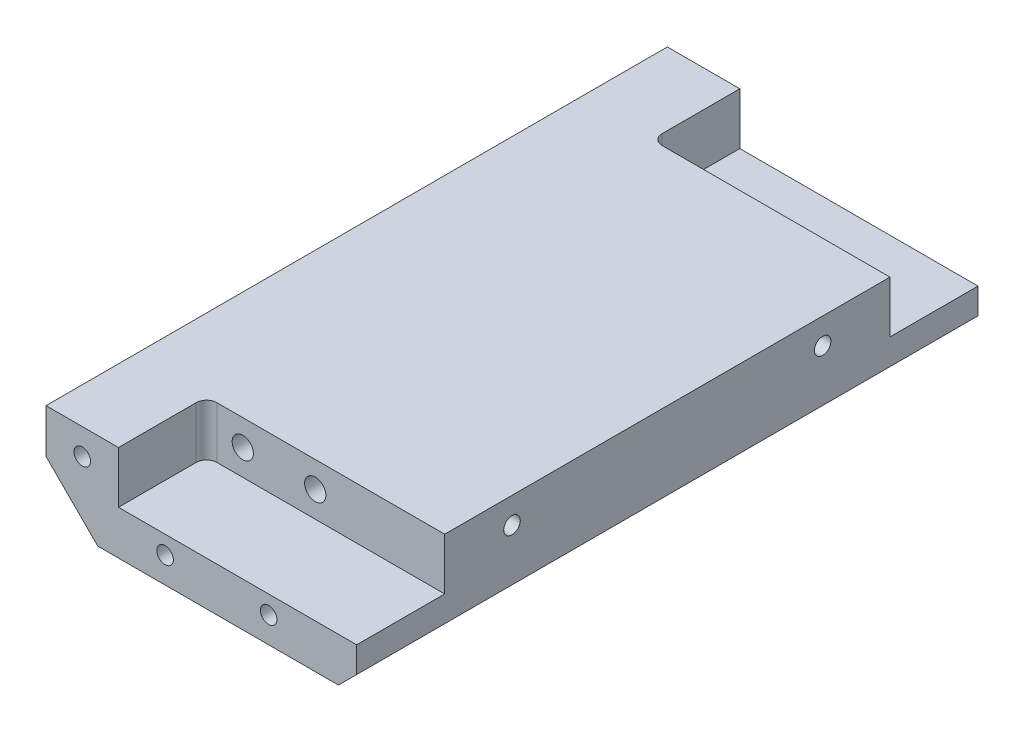
SolidWorks part; units mm, degrees
other "标注1"
sketch "草图22"
ref_plane "前视基准面" through (0, 0, 0) normal (0, 0, 1) x (1, 0, 0)
ref_plane "上视基准面" through (0, 0, 0) normal (0, 1, 0) x (1, 0, 0)
ref_plane "右视基准面" through (0, 0, 0) normal (1, 0, 0) x (0, 0, -1)
other "Configuration Table"
ref_plane "基准面1" through (0, 0, -30) normal (0, 0, -1) x (-1, 0, 0)
sketch "草图1" plane through (0, 0, -30) normal (0, 0, -1) x (-1, 0, 0)
  line L0 (9.25, 6.5) -> (-15.75, 6.5)
  line L1 (-15.75, 6.5) -> (-15.75, -3.55)
  line L2 (-15.75, -3.55) -> (3.45, -3.55)
  line L3 (3.45, -3.55) -> (9.25, 2.25)
  line L4 (9.25, 2.25) -> (9.25, 6.5)
  dimension "D1" = 19.2
  dimension "D2" = 25
  dimension "D3" = 5.8
  dimension "D4" = 10.05
extrude "凸台-拉伸1" add sketch "草图1" against normal blind 60
sketch "草图2" plane through (15.75, 0, 0) normal (1, 0, 0) x (0, 0, -1)
  line L0 (21.5, 6.5) -> (21.5, 1.5)
  line L1 (21.5, 1.5) -> (30, 1.5)
  line L2 (30, 1.5) -> (30, 6.5)
  line L3 (30, 6.5) -> (21.5, 6.5)
  line L4 (30, 6.5) -> (30, -3.55) construction
  line L5 (-30, 6.5) -> (30, 6.5) construction
  dimension "D1" = 8.5
  dimension "D2" = 5
extrude "切除-拉伸1" cut sketch "草图2" against normal blind 18
sketch "草图3" plane through (0, 6.5, 0) normal (0, 1, 0) x (-1, 0, 0)
  line L0 (-10.75, -21.5) -> (-10.75, -17.5)
  line L1 (-10.75, -17.5) -> (-15.75, -17.5)
  line L2 (-15.75, -17.5) -> (-15.75, -21.5)
  line L3 (-15.75, -21.5) -> (-10.75, -21.5)
  line L4 (2.25, -30) -> (2.25, -21.5) construction
  line L5 (2.25, -21.5) -> (-15.75, -21.5) construction
  dimension "D1" = 13
  dimension "D2" = 18
  dimension "D3" = 4
extrude "切除-拉伸2" cut sketch "草图3" against normal blind 5
sketch "草图4" plane through (0, 0, 30) normal (0, 0, 1) x (1, 0, 0)
  line L0 (-2.25, 1.5) -> (15.75, 1.5)
  line L1 (15.75, 1.5) -> (15.75, 6.5)
  line L2 (15.75, 6.5) -> (-2.25, 6.5)
  line L3 (-2.25, 6.5) -> (-2.25, 1.5)
  line L4 (-9.25, 2.25) -> (-9.25, 6.5) construction
  line L5 (15.75, -3.55) -> (-3.45, -3.55) construction
  dimension "D1" = 7
  dimension "D2" = 25
  dimension "D3" = 5.05
  dimension "D4" = 10.05
extrude "切除-拉伸3" cut sketch "草图4" against normal blind 8.5
sketch "草图5" plane through (0, 6.5, 0) normal (0, 1, 0) x (-1, 0, 0)
  line L0 (-15.75, 21.5) -> (-15.75, 17.5)
  line L1 (-15.75, 17.5) -> (-10.75, 17.5)
  line L2 (-10.75, 17.5) -> (-10.75, 21.5)
  line L3 (-10.75, 21.5) -> (-15.75, 21.5)
  line L4 (2.25, 21.5) -> (2.25, 30) construction
  line L5 (-15.75, 21.5) -> (2.25, 21.5) construction
  dimension "D1" = 13
  dimension "D2" = 18
  dimension "D3" = 4
extrude "切除-拉伸4" cut sketch "草图5" against normal blind 5
hole_wizard "Ø1.6 (1.6) 直径孔1" positions "草图7" profile "草图6" hole size "Ø1.6" standard "ANSI Metric"
sketch "草图7" plane through (15.75, 0, 0) normal (1, 0, 0) x (0, 0, -1)
  point P0 (-15, 4)
  point P1 (15, 4)
sketch "草图6" plane through (15.75, 4, 15) normal (0, 1, 0) x (0, 0, -1)
  line L0 (0, 0) -> (0, 5)
  line L1 (0, 5) -> (0.8, 5)
  line L2 (0.8, 5) -> (0.8, 0)
  line L5 (0.8, 0) -> (0, 0)
  line L10 (0, 5) -> (-0.8, 5) construction
  line L11 (0, -6.35) -> (0, 107.95) construction
  dimension "孔直径" = 1.6
  dimension "孔深度" = 5
  dimension "导头角度" = 180
hole_wizard "Ø2.05 (2.05) 直径孔1" positions "草图9" profile "草图8" hole size "Ø2.05" standard "ANSI Metric"
sketch "草图9" plane through (0, 0, 21.5) normal (0, 0, 1) x (1, 0, 0)
  point P0 (1.25, 4)
  point P1 (8.25, 4)
sketch "草图8" plane through (1.25, 4, 21.5) normal (1, 0, 0) x (0, -1, 0)
  line L0 (0, 0) -> (0, 7)
  line L1 (0, 7) -> (1.025, 7)
  line L2 (1.025, 7) -> (1.025, 0)
  line L5 (1.025, 0) -> (0, 0)
  line L10 (0, 7) -> (-1.025, 7) construction
  line L11 (0, -6.35) -> (0, 107.95) construction
  dimension "孔直径" = 2.05
  dimension "孔深度" = 7
  dimension "导头角度" = 180
hole_wizard "Ø1.6 (1.6) 直径孔2" positions "草图11" profile "草图10" hole size "Ø1.6" standard "ANSI Metric"
sketch "草图11" plane through (0, 0, 30) normal (0, 0, 1) x (1, 0, 0)
  point P0 (12.25, -0.25)
  point P1 (2.25, -0.25)
sketch "草图10" plane through (12.25, -0.25, 30) normal (1, 0, 0) x (0, -1, 0)
  line L0 (0, 0) -> (0, 7)
  line L1 (0, 7) -> (0.8, 7)
  line L2 (0.8, 7) -> (0.8, 0)
  line L5 (0.8, 0) -> (0, 0)
  line L10 (0, 7) -> (-0.8, 7) construction
  line L11 (0, -6.35) -> (0, 107.95) construction
  dimension "孔直径" = 1.6
  dimension "孔深度" = 7
  dimension "导头角度" = 180
hole_wizard "Ø1.6 (1.6) 直径孔3" positions "草图13" profile "草图12" hole size "Ø1.6" standard "ANSI Metric"
sketch "草图13" plane through (-9.25, 0, 0) normal (-1, 0, 0) x (0, 0, 1)
  point P0 (0, 4.375)
sketch "草图12" plane through (-9.25, 4.375, 0) normal (0, 1, 0) x (0, 0, 1)
  line L0 (0, 0) -> (0, 7)
  line L1 (0, 7) -> (0.8, 7)
  line L2 (0.8, 7) -> (0.8, 0)
  line L5 (0.8, 0) -> (0, 0)
  line L10 (0, 7) -> (-0.8, 7) construction
  line L11 (0, -6.35) -> (0, 107.95) construction
  dimension "孔直径" = 1.6
  dimension "孔深度" = 7
  dimension "导头角度" = 180
hole_wizard "Ø1.6 (1.6) 直径孔4" positions "草图15" profile "草图14" hole size "Ø1.6" standard "ANSI Metric"
sketch "草图15" plane through (-9.25, 0, 0) normal (-1, 0, 0) x (0, 0, 1)
  point P0 (-25, 4.375)
  point P1 (25, 4.375)
sketch "草图14" plane through (-9.25, 4.375, -25) normal (0, 1, 0) x (0, 0, 1)
  line L0 (0, 0) -> (0, 25)
  line L1 (0, 25) -> (0.8, 25)
  line L2 (0.8, 25) -> (0.8, 0)
  line L5 (0.8, 0) -> (0, 0)
  line L11 (0, -6.35) -> (0, 107.95) construction
  dimension "通孔孔直径" = 1.6
  dimension "通孔孔深度" = 25
hole_wizard "Ø1.6 (1.6) 直径孔5" positions "草图17" profile "草图16" hole size "Ø1.6" standard "ANSI Metric"
sketch "草图17" plane through (0, 0, -30) normal (0, 0, -1) x (-1, 0, 0)
  point P0 (-12.25, -0.25)
  point P1 (5.75, 4)
  point P2 (-2.25, -0.25)
sketch "草图16" plane through (12.25, -0.25, -30) normal (1, 0, 0) x (0, 1, 0)
  line L0 (0, 0) -> (0, 7)
  line L1 (0, 7) -> (0.8, 7)
  line L2 (0.8, 7) -> (0.8, 0)
  line L5 (0.8, 0) -> (0, 0)
  line L10 (0, 7) -> (-0.8, 7) construction
  line L11 (0, -6.35) -> (0, 107.95) construction
  dimension "孔直径" = 1.6
  dimension "孔深度" = 7
  dimension "导头角度" = 180
hole_wizard "Ø2.05 (2.05) 直径孔2" positions "草图19" profile "草图18" hole size "Ø2.05" standard "ANSI Metric"
sketch "草图19" plane through (0, 0, -21.5) normal (0, 0, -1) x (-1, 0, 0)
  point P0 (-8.25, 4)
  point P1 (-1.25, 4)
sketch "草图18" plane through (8.25, 4, -21.5) normal (1, 0, 0) x (0, 1, 0)
  line L0 (0, 0) -> (0, 7)
  line L1 (0, 7) -> (1.025, 7)
  line L2 (1.025, 7) -> (1.025, 0)
  line L5 (1.025, 0) -> (0, 0)
  line L10 (0, 7) -> (-1.025, 7) construction
  line L11 (0, -6.35) -> (0, 107.95) construction
  dimension "孔直径" = 2.05
  dimension "孔深度" = 7
  dimension "导头角度" = 180
ref_plane "基准面2" through (0, -0.75, 0) normal (0, -1, 0) x (-1, 0, 0)
hole_wizard "Ø6.0 (6) 直径孔1" positions "草图21" profile "草图20" hole size "Ø6.0" standard "ANSI Metric"
sketch "草图21" plane through (0, -0.75, 0) normal (0, -1, 0) x (-1, 0, 0)
  point P0 (9.25, 0)
  point P1 (9.25, 20)
  point P2 (9.25, -20)
sketch "草图20" plane through (-9.25, -0.75, 0) normal (1, 0, 0) x (0, 0, -1)
  line L0 (0, 0) -> (0, 3)
  line L1 (0, 3) -> (3, 3)
  line L2 (3, 3) -> (3, 0)
  line L5 (3, 0) -> (0, 0)
  line L10 (0, 3) -> (-3, 3) construction
  line L11 (0, -6.35) -> (0, 107.95) construction
  dimension "孔直径" = 6
  dimension "孔深度" = 3
  dimension "导头角度" = 180
chamfer "倒角2" distance 0.8 angle 45 2 edges at (6.15, -3.55, 30) (6.15, -3.55, -30)
fillet "圆角1" radius 1 2 edges at (-2.25, 4, 21.5) (-2.25, 4, -21.5) tangent propagation no
fillet "圆角2" radius 2.5 2 edges at (13.25, 6.5, -17.5) (13.25, 6.5, 17.5) tangent propagation no
sketch "草图23" plane through (10.75, 0, 0) normal (1, 0, 0) x (0, 0, -1)
  line L4 (-15, 6.5) -> (-21.5, 6.5)
  line L5 (-21.5, 6.5) -> (-21.5, 1.5)
  line L6 (-21.5, 1.5) -> (-17.5, 1.5)
  line L7 (-17.5, 1.5) -> (-17.5, 4)
  line L8 (-15, 6.5) -> (-21.5, 6.5)
  line L9 (-21.5, 6.5) -> (-21.5, 1.5)
  line L10 (-21.5, 1.5) -> (-17.5, 1.5)
  line L11 (-17.5, 1.5) -> (-17.5, 4)
  arc A1 (-15, 6.5) -> (-17.5, 4) centre (-15, 4) ccw
  arc A2 (-15, 6.5) -> (-17.5, 4) centre (-15, 4) ccw
  dimension "D1" = 0
extrude "凸台-拉伸2" add sketch "草图23" along normal up to surface (5 mm away) up to face at (15.75, 4, 14.2)
sketch "草图24" plane through (10.75, 0, 0) normal (1, 0, 0) x (0, 0, -1)
  line L4 (21.5, 6.5) -> (15, 6.5)
  line L5 (17.5, 4) -> (17.5, 1.5)
  line L6 (17.5, 1.5) -> (21.5, 1.5)
  line L7 (21.5, 1.5) -> (21.5, 6.5)
  line L8 (21.5, 6.5) -> (15, 6.5)
  line L9 (17.5, 4) -> (17.5, 1.5)
  line L10 (17.5, 1.5) -> (21.5, 1.5)
  line L11 (21.5, 1.5) -> (21.5, 6.5)
  arc A1 (17.5, 4) -> (15, 6.5) centre (15, 4) ccw
  arc A2 (17.5, 4) -> (15, 6.5) centre (15, 4) ccw
  dimension "D1" = 0
extrude "凸台-拉伸3" add sketch "草图24" along normal up to surface (5 mm away) up to face at (15.75, 0.9925, -0.6834)
sketch "草图26" plane through (15.75, 0, 0) normal (1, 0, 0) x (0, 0, -1)
  line L10 (30, 1.5) -> (21.5, 1.5)
  line L11 (21.5, 1.5) -> (21.5, 6.5)
  line L12 (21.5, 6.5) -> (-21.5, 6.5)
  line L13 (-21.5, 6.5) -> (-21.5, 1.5)
  line L14 (-21.5, 1.5) -> (-30, 1.5)
  line L15 (-30, 1.5) -> (-30, -2.75)
  line L16 (-30, -2.75) -> (-29.2, -3.55)
  line L17 (-29.2, -3.55) -> (29.2, -3.55)
  line L18 (29.2, -3.55) -> (30, -2.75)
  line L19 (30, -2.75) -> (30, 1.5)
  line L20 (30, 1.5) -> (21.5, 1.5)
  line L21 (21.5, 1.5) -> (21.5, 6.5)
  line L22 (21.5, 6.5) -> (-21.5, 6.5)
  line L23 (-21.5, 6.5) -> (-21.5, 1.5)
  line L24 (-21.5, 1.5) -> (-30, 1.5)
  line L25 (-30, 1.5) -> (-30, -2.75)
  line L26 (-30, -2.75) -> (-29.2, -3.55)
  line L27 (-29.2, -3.55) -> (29.2, -3.55)
  line L28 (29.2, -3.55) -> (30, -2.75)
  line L29 (30, -2.75) -> (30, 1.5)
  circle A0 centre (15, 4) radius 0.8 construction
  circle A1 centre (-15, 4) radius 0.8 construction
  circle A2 centre (15, 4) radius 0.8
  circle A3 centre (-15, 4) radius 0.8
  dimension "D1" = 0
extrude "凸台-拉伸5" add sketch "草图26" along normal blind 5
chamfer "倒角3" distance 2.5596 angle 45 1 edges at (20.75, -3.55, 0)
sketch "草图27" plane through (-2.25, 0, 0) normal (1, 0, 0) x (0, 0, -1)
  circle A0 centre (25, 4.375) radius 0.8 construction
  circle A1 centre (-25, 4.375) radius 0.8 construction
  circle A2 centre (25, 4.375) radius 0.8
  circle A3 centre (-25, 4.375) radius 0.8
extrude "凸台-拉伸6" add sketch "草图27" against normal blind 1
sketch "草图28" plane through (0, 0, 30) normal (0, 0, 1) x (1, 0, 0)
  circle A0 centre (-5.75, 4) radius 0.8 construction
  circle A1 centre (-5.75, 4) radius 0.8
extrude "切除-拉伸5" cut sketch "草图28" against normal blind 7
